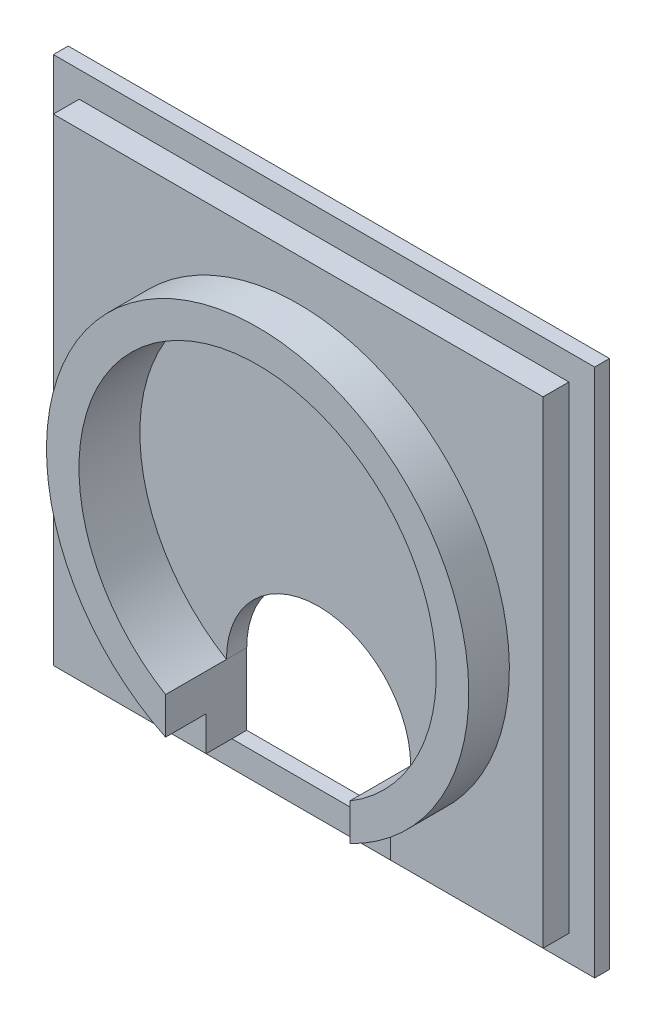
SolidWorks part; units mm, degrees
material "ABS"
ref_plane "Front Plane" through (0, 0, 0) normal (0, 0, 1) x (1, 0, 0)
ref_plane "Top Plane" through (0, 0, 0) normal (0, 1, 0) x (1, 0, 0)
ref_plane "Right Plane" through (0, 0, 0) normal (1, 0, 0) x (0, 0, -1)
sketch "Sketch16" plane through (0, 0, 0) normal (0, 0, 1) x (1, 0, 0)
  line L6 (-30.15, 31.15) -> (30.15, 31.15)
  line L11 (-30.15, 31.15) -> (-30.15, -27.65)
  line L12 (-30.15, -27.65) -> (30.15, -27.65)
  line L13 (30.15, 31.15) -> (30.15, -27.65)
  circle A0 centre (0, 0) radius 22
extrude "Boss-Extrude2" add sketch "Sketch16" against normal blind 5
sketch "Sketch22" plane through (0, 31.15, 0) normal (0, 1, 0) x (1, 0, 0)
  line L0 (30.15, 5) -> (30.15, 2.5)
  line L1 (30.15, 5) -> (30.15, 0) construction
  line L2 (30.15, 2.5) -> (-30.15, 2.5)
  line L3 (-30.15, 5) -> (-30.15, 0) construction
  line L4 (-30.15, 2.5) -> (-30.15, 5)
  line L5 (-30.15, 5) -> (30.15, 5)
extrude "Boss-Extrude7" add sketch "Sketch22" against normal blind 50
sketch "Sketch23" plane through (0, 0, 0) normal (0, 0, 1) x (1, 0, 0)
  line L0 (-11.3436, -23.3949) -> (-11.3436, -18.85)
  line L1 (22, -13.8564) -> (22, 0)
  line L2 (11.3436, -23.3949) -> (11.3436, -18.85)
  circle A0 centre (0, 0) radius 22
  circle A1 centre (0, 0) radius 26
  point P10 (-7.9411, -20.5168)
  point P11 (-13.4752, -17.3902)
  point P12 (0, 0)
  circle M1 centre (0, 0) radius 22
  dimension "D1" = 52
  dimension "D2" = 44
extrude "Boss-Extrude8" add sketch "Sketch23" along normal blind 5 contours L1 A1 L0 M1 | L2 A1 L1 M1 region at (-13.4226, 21.4255, 0) region at (17.4163, -15.5097, 0)
ref_plane "Plane1" through (0, 0, -3.175) normal (0, 0, 1) x (1, 0, 0)
sketch "Sketch27" plane through (0, 0, -3.175) normal (0, 0, 1) x (1, 0, 0)
  line L0 (30.15, 31.15) -> (-30.15, 31.15) construction
  line L1 (33.325, 34.325) -> (-33.325, 34.325)
  line L2 (33.325, 34.325) -> (33.325, -30.825)
  line L3 (33.325, -30.825) -> (-33.325, -30.825)
  line L4 (-33.325, 34.325) -> (-33.325, -30.825)
  line L5 (-30.15, 31.15) -> (-30.15, -27.65) construction
  line L6 (30.15, -27.65) -> (30.15, 31.15) construction
  line L7 (-30.15, -27.65) -> (30.15, -27.65) construction
  point P4 (0, 34.325)
  point P7 (0, 31.15)
  point P8 (-33.325, 1.75)
  point P11 (-30.15, 1.75)
  point P12 (-38.7387, -32.1357)
  point P13 (-42.466, -32.279)
  point P14 (0, 0)
  dimension "D1" = 3.175
  dimension "D2" = 3.175
extrude "Boss-Extrude10" add sketch "Sketch27" against normal up to surface (1.825 mm away) up to face at (0, -20.425, -5)
sketch "Sketch24" plane through (0, 0, -2.5) normal (0, 0, 1) x (1, 0, 0)
  line L0 (-30.15, -27.65) -> (30.15, -27.65) construction
  line L1 (-11.3436, -18.85) -> (11.3436, -18.85) construction
  line L4 (-11.3436, -18.85) -> (-11.3436, -27.65)
  line L5 (-11.3436, -27.65) -> (11.3436, -27.65)
  line L6 (11.3436, -18.85) -> (11.3436, -27.65)
  arc A0 (11.3436, -18.85) -> (-11.3436, -18.85) centre (0, 0) ccw construction
  arc A1 (-11.3436, -18.85) -> (11.3436, -18.85) centre (0, -18.85) cw
extrude "Cut-Extrude3" cut sketch "Sketch24" against normal mid plane 52.75
